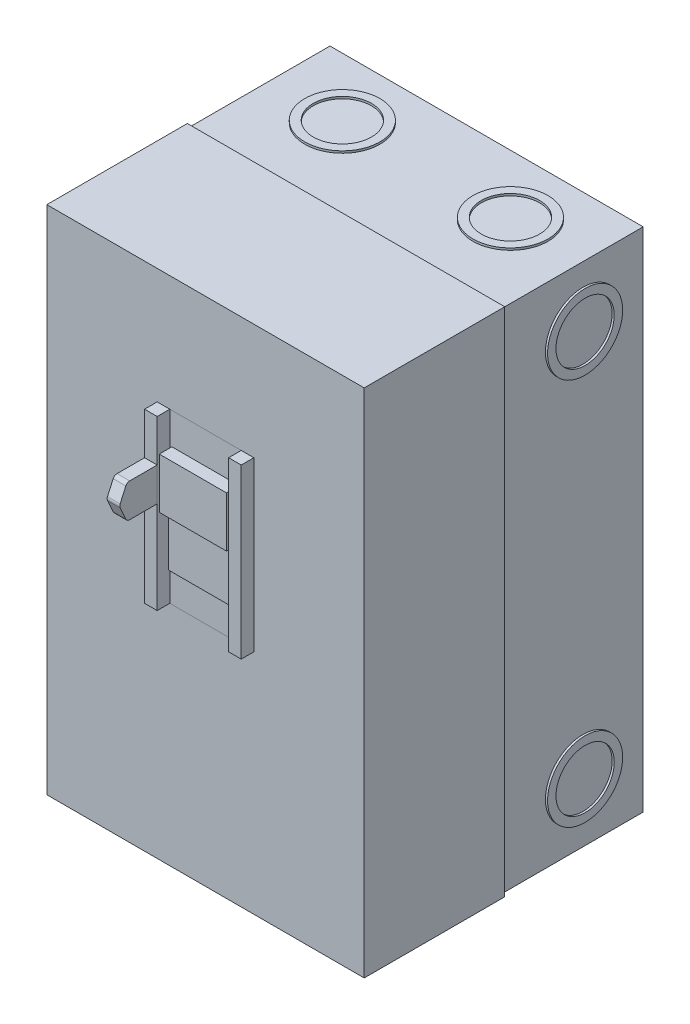
SolidWorks part; units mm, degrees
ref_plane "Front Plane" through (0, 0, 0) normal (0, 0, 1) x (1, 0, 0)
ref_plane "Top Plane" through (0, 0, 0) normal (0, 1, 0) x (1, 0, 0)
ref_plane "Right Plane" through (0, 0, 0) normal (1, 0, 0) x (0, 0, -1)
sketch "Sketch2" plane through (0, 0, 0) normal (1, 0, 0) x (0, 0, -1)
  line L0 (0, 0) -> (0, -95123.7541) construction
  line L1 (0, 0) -> (-95123.7541, 0) construction
  line L2 (0, -95.7262) -> (0, 95.7262)
  line L3 (0, 95.7262) -> (-53.086, 95.7262)
  line L4 (-53.086, 95.7262) -> (-53.086, 96.52)
  line L5 (-53.086, 96.52) -> (-106.172, 96.52)
  line L6 (-106.172, 96.52) -> (-106.172, -96.52)
  line L7 (-106.172, 0) -> (-110.9345, 0)
  line L8 (-53.086, -95.7262) -> (-53.086, -96.52)
  line L9 (0, -95.7262) -> (-53.086, -95.7262)
  line L10 (-53.086, -96.52) -> (-106.172, -96.52)
  line L11 (-53.086, 95.7262) -> (-53.086, -95.7262) construction
  line L12 (0, 0) -> (3.175, 0)
  line L13 (-22.733, 95.7262) -> (-22.733, -95.7262) construction
  circle A0 centre (-22.733, 73.152) radius 11.0109
  circle A1 centre (-22.733, 73.152) radius 14.1859
  circle A2 centre (-22.733, -73.152) radius 14.1859
  circle A3 centre (-22.733, -73.152) radius 11.0109
  point P13 (0, 0)
  dimension "D1" = 3.175
sketch "Sketch3" plane through (0, 0, 0) normal (0, 0, 1) x (1, 0, 0)
  line L0 (0, 0) -> (-49231.0849, 0) construction
  line L1 (0, 0) -> (0, -49231.0849) construction
  line L3 (31.75, 95.7262) -> (31.75, -95.7262) construction
  line L4 (-18.2563, 52.832) -> (18.2562, 52.832)
  line L5 (-18.2563, 52.832) -> (-18.2562, -10.668)
  line L6 (-18.2562, -10.668) -> (18.2563, -10.668)
  line L7 (18.2562, 52.832) -> (18.2563, -10.668)
  line L8 (-18.2563, 52.832) -> (18.2563, -10.668) construction
  line L9 (-18.2562, -10.668) -> (18.2562, 52.832) construction
  line L10 (-59.944, 95.7262) -> (59.944, 95.7262)
  line L11 (-59.944, 95.7262) -> (-59.944, -95.7262)
  line L12 (-59.944, -95.7262) -> (59.944, -95.7262)
  line L13 (59.944, 95.7262) -> (59.944, -95.7262)
  line L14 (-59.944, 95.7262) -> (59.944, -95.7262) construction
  line L15 (-59.944, -95.7262) -> (59.944, 95.7262) construction
  circle A0 centre (41.275, 76.2) radius 2.794
  circle A1 centre (-41.275, 76.2) radius 2.794
  circle A2 centre (41.275, -76.2) radius 2.794
  circle A3 centre (-41.275, -76.2) radius 2.794
  point P5 (-41.275, 76.2)
  point P6 (41.275, 76.2)
  point P7 (41.275, -76.2)
  point P8 (-41.275, -76.2)
  point P9 (0, 21.082)
  point P14 (0, 0)
  dimension "MOUNTING HOLE DIA" = 5.588
  dimension "MOUNTING HOLE VERTICAL DISTANCE" = 152.4
  dimension "MOUNTING HOLE HORIZONTAL DISTANCE" = 82.55
  dimension "BUTTON CAVITY DISTANCE FROM CENTER" = 21.082
  dimension "BUTTON CAVITY HEIGHT" = 63.5
  dimension "BUTTON CAVITY WIDTH" = 36.5125
  dimension "BOX WIDTH" = 119.888
  dimension "HORIZONTAL KNOCKOUT DISTANCE FROM CENTER" = 31.75
sketch "Sketch4" plane through (0, 0, 0) normal (0, 0, 1) x (1, 0, 0)
  line L0 (59.944, 95.7262) -> (59.944, -95.7262) construction
  line L1 (-59.1502, -95.7262) -> (59.1502, -95.7262)
  line L2 (-59.1502, -95.7262) -> (-59.1502, 95.7262)
  line L3 (-59.1502, 95.7262) -> (59.1502, 95.7262)
  line L4 (59.1502, -95.7262) -> (59.1502, 95.7262)
  line L5 (-59.1502, -95.7262) -> (59.1502, 95.7262) construction
  line L6 (-59.1502, 95.7262) -> (59.1502, -95.7262) construction
  point P0 (0, 0)
  dimension "D1" = 0.7937
extrude "Boss-Extrude1" add sketch "Sketch4" along normal up to vertex (53.086 mm away) up to point (0, 95.7262, 53.086)
sketch "Sketch5" plane through (0, 0, 53.086) normal (0, 0, 1) x (1, 0, 0)
  line L0 (59.944, 95.7262) -> (59.944, -95.7262) construction
  line L1 (-59.944, -96.52) -> (59.944, -96.52)
  line L2 (-59.944, -96.52) -> (-59.944, 96.52)
  line L3 (-59.944, 96.52) -> (59.944, 96.52)
  line L4 (59.944, -96.52) -> (59.944, 96.52)
  line L5 (-59.944, -96.52) -> (59.944, 96.52) construction
  line L6 (-59.944, 96.52) -> (59.944, -96.52) construction
  point P0 (0, 0)
extrude "Boss-Extrude2" add sketch "Sketch5" along normal up to vertex (53.086 mm away) up to point (0, 96.52, 106.172)
sketch "Sketch6" plane through (0, 0, 0) normal (0, 0, -1) x (-1, 0, 0)
  circle A0 centre (41.275, 73.025) radius 12.7
  circle A1 centre (-41.275, 73.025) radius 12.7
  circle A2 centre (41.275, -76.2) radius 9.525
  circle A3 centre (-41.275, -76.2) radius 9.525
  dimension "D1" = 25.4
  dimension "D2" = 19.05
  dimension "D3" = 3.175
extrude "Boss-Extrude3" add sketch "Sketch6" along normal blind 3.175
fillet "Fillet1" radius 3.175 4 edges at (31.75, -76.2, -3.175) (-50.8, -76.2, -3.175) (-53.975, 73.025, -3.175) (28.575, 73.025, -3.175)
sketch "Sketch7" plane through (0, 0, -3.175) normal (0, 0, -1) x (-1, 0, 0)
  circle A0 centre (-41.275, 76.2) radius 2.794 construction
  circle A1 centre (41.275, 76.2) radius 2.794 construction
  circle A2 centre (41.275, -76.2) radius 2.794 construction
  circle A3 centre (-41.275, -76.2) radius 2.794 construction
  circle A4 centre (-41.275, 76.2) radius 2.794
  circle A5 centre (41.275, 76.2) radius 2.794
  circle A6 centre (41.275, -76.2) radius 2.794
  circle A7 centre (-41.275, -76.2) radius 2.794
extrude "Cut-Extrude1" cut sketch "Sketch7" against normal blind 6.35
sketch "Sketch8" plane through (0, 0, -3.175) normal (0, 0, -1) x (-1, 0, 0)
  line L0 (-41.275, 76.2) -> (-41.275, 69.0563) construction
  line L1 (-46.3991, 71.2047) -> (-43.8517, 77.2803)
  line L2 (-38.6983, 77.2803) -> (-36.1509, 71.2047)
  line L3 (0, 95.7263) -> (0, -95.7262) construction
  line L4 (59.944, 95.7262) -> (-59.944, 95.7262) construction
  line L5 (59.944, -95.7262) -> (-59.944, -95.7262) construction
  line L6 (41.275, 76.2) -> (41.275, 69.0563) construction
  line L7 (38.6983, 77.2803) -> (36.1509, 71.2047)
  line L8 (46.3991, 71.2047) -> (43.8517, 77.2803)
  arc A0 (-46.3991, 71.2047) -> (-36.1509, 71.2047) centre (-41.275, 69.0563) ccw
  arc A1 (43.8517, 77.2803) -> (38.6983, 77.2803) centre (41.275, 76.2) ccw
  circle A2 centre (-41.275, 76.2) radius 2.794 construction
  arc A3 (-43.8517, 77.2803) -> (-38.6983, 77.2803) centre (-41.275, 76.2) cw
  arc A4 (46.3991, 71.2047) -> (36.1509, 71.2047) centre (41.275, 69.0563) cw
  dimension "D1" = 5.5562
  dimension "D2" = 7.1437
extrude "Cut-Extrude2" cut sketch "Sketch8" against normal up to surface (6.35 mm away) up to face at (-44.069, 76.2, 3.175)
sketch "Sketch9" plane through (59.1502, 0, 0) normal (1, 0, 0) x (0, 0, -1)
  line L4 (0, -95.7262) -> (0, 95.7262)
  line L5 (0, 95.7262) -> (-53.086, 95.7262)
  line L6 (-53.086, 95.7262) -> (-53.086, -95.7262)
  line L7 (-53.086, -95.7262) -> (0, -95.7262)
  line L8 (0, -95.7262) -> (0, 95.7262)
  line L9 (0, 95.7262) -> (-53.086, 95.7262)
  line L10 (-53.086, 95.7262) -> (-53.086, -95.7262)
  line L11 (-53.086, -95.7262) -> (0, -95.7262)
  circle A0 centre (-22.733, 73.152) radius 14.1859 construction
  circle A1 centre (-22.733, 73.152) radius 14.1859
  circle A2 centre (-22.733, 73.152) radius 11.0109 construction
  circle A3 centre (-22.733, -73.152) radius 11.0109 construction
  circle A4 centre (-22.733, -73.152) radius 14.1859 construction
  circle A5 centre (-22.733, 73.152) radius 11.0109
  circle A6 centre (-22.733, -73.152) radius 11.0109
  circle A7 centre (-22.733, -73.152) radius 14.1859
  dimension "D1" = 0
extrude "Boss-Extrude4" add sketch "Sketch9" along normal up to vertex (0.7937 mm away) contours A1 A5 | A7 A6 region at (59.1502, 73.152, 36.5177) region at (59.1502, -73.152, 36.5177) up to point (59.944, 95.7262, 0)
mirror "Mirror1" about plane through (0, 0, 0) normal (1, 0, 0) of "Boss-Extrude4"
sketch "Sketch10" plane through (0, 95.7262, 0) normal (0, 1, 0) x (1, 0, 0)
  line L0 (-59.1502, -22.733) -> (59.1502, -22.733) construction
  line L1 (-59.1502, -53.086) -> (-59.1502, 0) construction
  line L2 (59.1502, -53.086) -> (59.1502, 0) construction
  line L3 (0, 0) -> (0, -50.546) construction
  line L4 (-59.944, 0) -> (59.944, 0) construction
  line L5 (0, 0) -> (0, -53.086) construction
  circle A0 centre (31.75, -22.733) radius 11.0109
  circle A1 centre (31.75, -22.733) radius 14.1859
  circle A2 centre (-31.75, -22.733) radius 14.1859
  circle A3 centre (-31.75, -22.733) radius 11.0109
  dimension "D1" = 3.175
  dimension "D2" = 22.0218
extrude "Boss-Extrude5" add sketch "Sketch10" along normal up to vertex (0.7937 mm away) up to point (0, 96.52, 53.086)
mirror "Mirror2" about plane through (0, 0, 0) normal (0, 1, 0) of "Boss-Extrude5"
sketch "Sketch11" plane through (0, 0, 106.172) normal (0, 0, 1) x (1, 0, 0)
  line L0 (-18.2563, 52.832) -> (-18.2562, -10.668) construction
  line L1 (-18.2562, -10.668) -> (18.2563, -10.668) construction
  line L2 (18.2562, 52.832) -> (18.2563, -10.668) construction
  line L3 (-18.2563, 52.832) -> (18.2562, 52.832) construction
  line L4 (59.944, -96.52) -> (59.944, 96.52)
  line L5 (59.944, 96.52) -> (-59.944, 96.52)
  line L6 (-59.944, 96.52) -> (-59.944, -96.52)
  line L7 (-59.944, -96.52) -> (59.944, -96.52)
  line L8 (59.944, -96.52) -> (59.944, 96.52)
  line L9 (59.944, 96.52) -> (-59.944, 96.52)
  line L10 (-59.944, 96.52) -> (-59.944, -96.52)
  line L11 (-59.944, -96.52) -> (59.944, -96.52)
  line L12 (-18.2563, 52.832) -> (-18.2562, -10.668)
  line L13 (-18.2562, -10.668) -> (18.2563, -10.668)
  line L14 (18.2562, 52.832) -> (18.2563, -10.668)
  line L15 (-18.2563, 52.832) -> (18.2562, 52.832)
  dimension "D1" = 0
extrude "Cut-Extrude3" cut sketch "Sketch11" against normal blind 1.27 contours L15 L12 L13 L14 region at (0, 21.082, 106.172)
sketch "Sketch12" plane through (0, 52.832, 0) normal (0, -1, 0) x (1, 0, 0)
  line L0 (-18.2562, 104.902) -> (-18.2562, 110.9345)
  line L1 (-18.2562, 110.9345) -> (-13.4937, 110.9345)
  line L2 (-13.4937, 110.9345) -> (-13.4937, 106.172)
  line L3 (-59.944, 106.172) -> (59.944, 106.172) construction
  line L4 (-13.4937, 106.172) -> (0, 106.172)
  line L5 (0, 104.902) -> (0, 53.086) construction
  line L6 (-18.2562, 104.902) -> (18.2563, 104.902) construction
  line L7 (-59.944, 53.086) -> (59.944, 53.086) construction
  line L8 (-18.2562, 104.902) -> (0, 104.902)
  line L9 (13.4937, 106.172) -> (0, 106.172)
  line L10 (13.4937, 110.9345) -> (13.4937, 106.172)
  line L11 (18.2562, 110.9345) -> (13.4937, 110.9345)
  line L12 (18.2563, 104.902) -> (18.2562, 110.9345)
  line L13 (18.2563, 104.902) -> (0, 104.902)
  dimension "D1" = 26.9875
extrude "Boss-Extrude6" add sketch "Sketch12" along normal up to surface (63.5 mm away) separate body up to face at (0, -10.668, 105.537)
sketch "Sketch13" plane through (0, 0, 106.172) normal (0, 0, 1) x (1, 0, 0)
  line L0 (-13.4938, 21.082) -> (13.4938, 21.082) construction
  line L1 (-13.4937, -10.668) -> (-13.4937, 52.832) construction
  line L2 (13.4937, -10.668) -> (13.4937, 52.832) construction
  line L3 (0, 52.832) -> (0, -10.668) construction
  line L4 (-18.2563, 52.832) -> (18.2562, 52.832) construction
  line L5 (-18.2562, -10.668) -> (18.2563, -10.668) construction
  line L6 (12.7, 40.9258) -> (-12.7, 40.9258)
  line L7 (12.7, 20.2882) -> (-12.7, 20.2882)
  line L8 (12.7, 20.2882) -> (12.7, 1.2382)
  line L9 (12.7, 1.2382) -> (-12.7, 1.2382)
  line L10 (-12.7, 20.2882) -> (-12.7, 1.2382)
  line L11 (12.7, 20.2882) -> (-12.7, 1.2382) construction
  line L12 (12.7, 1.2382) -> (-12.7, 20.2882) construction
  line L13 (-12.7, 21.8758) -> (-12.7, 40.9258)
  line L14 (12.7, 21.8758) -> (-12.7, 21.8758)
  line L15 (12.7, 21.8758) -> (12.7, 40.9258)
  line L16 (12.7, 40.9258) -> (-12.7, 21.8758) construction
  line L17 (12.7, 21.8758) -> (-12.7, 40.9258) construction
  point P12 (0, 10.7632)
  point P21 (0, 31.4008)
  dimension "D1" = 25.4
  dimension "D2" = 19.05
  dimension "D3" = 11.9062
extrude "Cut-Extrude4" cut sketch "Sketch13" against normal up to next (1.27 mm away)
sketch "Sketch14" plane through (0, 0, 104.902) normal (0, 0, 1) x (1, 0, 0)
  line L0 (-12.7, 21.8758) -> (12.7, 21.8758) construction
  line L1 (12.7, 21.8758) -> (12.7, 40.9258) construction
  line L2 (12.7, 40.9258) -> (-12.7, 40.9258) construction
  line L3 (-12.7, 40.9258) -> (-12.7, 21.8758) construction
  line L4 (-12.7, 21.8758) -> (12.7, 21.8758)
  line L5 (12.7, 21.8758) -> (12.7, 40.9258)
  line L6 (12.7, 40.9258) -> (-12.7, 40.9258)
  line L7 (-12.7, 40.9258) -> (-12.7, 21.8758)
extrude "Boss-Extrude7" add sketch "Sketch14" along normal up to surface (6.0325 mm away) separate body up to face at (15.875, 21.082, 110.9345)
sketch "Sketch15" plane through (0, 0, 104.902) normal (0, 0, 1) x (1, 0, 0)
  line L4 (12.7, 20.2882) -> (12.7, 1.2382)
  line L5 (-12.7, 20.2882) -> (12.7, 20.2882)
  line L6 (-12.7, 20.2882) -> (-12.7, 1.2382)
  line L7 (12.7, 1.2382) -> (-12.7, 1.2382)
  line L8 (12.7, 20.2882) -> (-12.7, 20.2882) construction
  line L9 (12.7, 1.2382) -> (12.7, 20.2882) construction
  line L10 (-12.7, 1.2382) -> (12.7, 1.2382) construction
extrude "Boss-Extrude8" add sketch "Sketch15" along normal offset from surface (2.54 mm away) 1.27 separate body up to face at (0, 31.4008, 106.172) offset beyond the face yes
sketch "Sketch16" plane through (-18.2562, 0, 0) normal (-1, 0, 0) x (0, 0, 1)
  line L0 (110.9345, 30.607) -> (125.222, 30.607) construction
  line L1 (110.9345, -10.668) -> (110.9345, 52.832) construction
  line L2 (124.9288, 31.2585) -> (122.7857, 36.021)
  line L3 (121.338, 36.957) -> (110.9345, 36.957)
  line L4 (124.9288, 29.9555) -> (122.7857, 25.193)
  line L5 (121.338, 24.257) -> (110.9345, 24.257)
  line L6 (110.9345, 36.957) -> (110.9345, 24.257)
  line L7 (110.9345, 52.832) -> (104.902, 52.832) construction
  arc A0 (122.7857, 25.193) -> (121.338, 24.257) centre (121.338, 25.8445) cw
  arc A1 (124.9288, 31.2585) -> (124.9288, 29.9555) centre (123.4812, 30.607) cw
  arc A2 (122.7857, 36.021) -> (121.338, 36.957) centre (121.338, 35.3695) ccw
  point P12 (122.3645, 24.257)
  point P18 (122.3645, 36.957)
  dimension "D4" = 1.5875
  dimension "D1" = 15.875
  dimension "D2" = 12.7
  dimension "D3" = 14.2875
  dimension "D5" = 11.43
extrude "Boss-Extrude9" add sketch "Sketch16" against normal up to surface (4.7625 mm away) separate body up to face at (-13.4937, 21.082, 108.5532)
sketch "Sketch17" plane through (0, 0, 0) normal (1, 0, 0) x (0, 0, -1)
  line L0 (-36.576, -95.7262) -> (-52.451, -95.7262)
  line L1 (0, -95.7262) -> (-53.086, -95.7262) construction
  line L2 (-52.451, -95.7262) -> (-52.451, -111.6013)
  line L3 (-52.451, -111.6013) -> (-50.8635, -111.6013)
  line L4 (-50.8635, -111.6013) -> (-50.8635, -97.3137)
  line L5 (-50.8635, -97.3137) -> (-36.576, -97.3137)
  line L6 (-36.576, -97.3137) -> (-36.576, -95.7262)
  line L7 (-69.596, -96.52) -> (-69.596, -112.395)
  line L8 (-53.086, -96.52) -> (-106.172, -96.52) construction
  line L9 (-69.596, -112.395) -> (-68.0085, -112.395)
  line L10 (-68.0085, -112.395) -> (-68.0085, -98.1075)
  line L11 (-68.0085, -98.1075) -> (-55.3085, -98.1075)
  line L12 (-55.3085, -98.1075) -> (-55.3085, -112.395)
  line L13 (-55.3085, -112.395) -> (-53.721, -112.395)
  line L14 (-53.721, -112.395) -> (-53.721, -96.52)
  line L15 (-53.721, -96.52) -> (-69.596, -96.52)
  line L16 (-61.6585, -98.1075) -> (-61.6585, -96.52) construction
  line L17 (-53.086, -95.7262) -> (-53.086, -96.52) construction
  dimension "D1" = 15.875
  dimension "D2" = 0.635
  dimension "D3" = 0.635
  dimension "D4" = 1.5875
extrude "Boss-Extrude10" add sketch "Sketch17" along normal mid plane 38.1 separate body
fillet "Fillet2" radius 3.175 4 edges at (-19.05, -111.6013, 51.6572) (-19.05, -96.52, 36.576) (19.05, -96.52, 36.576) (19.05, -111.6013, 51.6572)
sketch "Sketch18" plane through (0, 0, 55.3085) normal (0, 0, 1) x (1, 0, 0)
  line L0 (-19.05, -98.1075) -> (-19.05, -112.395) construction
  line L1 (19.05, -112.395) -> (-3.175, -112.395)
  line L2 (19.05, -112.395) -> (19.05, -101.2825)
  line L3 (19.05, -101.2825) -> (-3.175, -101.2825)
  line L4 (-3.175, -112.395) -> (-3.175, -101.2825)
  dimension "D1" = 15.875
  dimension "D2" = 11.1125
extrude "Cut-Extrude5" cut sketch "Sketch18" against normal blind 38.1
sketch "Sketch19" plane through (0, 0, 69.596) normal (0, 0, 1) x (1, 0, 0)
  line L0 (19.05, -96.52) -> (-19.05, -96.52) construction
  line L1 (-19.05, -112.395) -> (3.175, -112.395)
  line L2 (-19.05, -112.395) -> (-19.05, -96.52)
  line L3 (-19.05, -96.52) -> (3.175, -96.52)
  line L4 (3.175, -112.395) -> (3.175, -96.52)
  line L5 (19.05, -96.52) -> (19.05, -112.395) construction
  dimension "D1" = 15.875
extrude "Cut-Extrude6" cut sketch "Sketch19" against normal blind 3.175
fillet "Fillet3" radius 3.175 6 edges at (-3.175, -101.2825, 54.5147) (-19.05, -97.3137, 66.421) (19.05, -112.395, 68.8022) (3.175, -112.395, 68.8023) (-3.175, -112.395, 54.5147) (-19.05, -112.395, 54.5147)
sketch "Sketch20" plane through (0, 0, 55.3085) normal (0, 0, 1) x (1, 0, 0)
  line L0 (-11.1125, -112.395) -> (-11.1125, -98.1075) construction
  line L1 (-6.35, -112.395) -> (-15.875, -112.395) construction
  line L2 (19.05, -98.1075) -> (-19.05, -98.1075) construction
  circle A0 centre (-11.1125, -105.2512) radius 5.08
  dimension "D1" = 10.16
extrude "Cut-Extrude7" cut sketch "Sketch20" against normal through all
sketch "Sketch21" plane through (0, 0, 69.596) normal (0, 0, 1) x (1, 0, 0)
  line L0 (11.1125, -112.395) -> (11.1125, -96.52) construction
  line L1 (15.875, -112.395) -> (6.35, -112.395) construction
  line L2 (19.05, -96.52) -> (3.175, -96.52) construction
  circle A0 centre (11.1125, -104.4575) radius 2.159
  dimension "D1" = 4.318
extrude "Cut-Extrude8" cut sketch "Sketch21" against normal through all
sketch "Sketch22" plane through (0, 0, 69.596) normal (0, 0, 1) x (1, 0, 0)
  line L1 (6.5298, -104.4575) -> (8.8211, -108.4262)
  line L2 (8.8211, -108.4262) -> (13.4039, -108.4262)
  line L3 (13.4039, -108.4262) -> (15.6952, -104.4575)
  line L4 (15.6952, -104.4575) -> (13.4039, -100.4887)
  line L5 (13.4039, -100.4887) -> (8.8211, -100.4887)
  line L6 (8.8211, -100.4887) -> (6.5298, -104.4575)
  circle A0 centre (11.1125, -104.4575) radius 3.9687 construction
  dimension "D1" = 7.9375
extrude "Boss-Extrude11" add sketch "Sketch22" along normal blind 3.175 separate body
sketch "Sketch23" plane through (0, -108.4263, 0) normal (0, -1, 0) x (1, 0, 0)
  line L0 (11.1125, 72.771) -> (11.1125, 69.596) construction
  line L1 (8.8211, 72.771) -> (13.4039, 72.771) construction
  line L2 (15.875, 69.596) -> (6.35, 69.596) construction
  line L4 (11.43, 71.501) -> (10.795, 71.501)
  line L5 (11.43, 71.501) -> (11.43, 72.771)
  line L6 (11.43, 72.771) -> (10.795, 72.771)
  line L7 (10.795, 71.501) -> (10.795, 72.771)
  line L8 (11.43, 71.501) -> (10.795, 72.771) construction
  line L9 (11.43, 72.771) -> (10.795, 71.501) construction
  point P6 (11.1125, 72.136)
  dimension "D1" = 0.635
  dimension "D2" = 1.27
extrude "Cut-Extrude9" cut sketch "Sketch23" against normal up to next (7.9375 mm away)
sketch "Sketch24" plane through (0, 0, 69.596) normal (0, 0, -1) x (-1, 0, 0)
  line L6 (-6.5298, -104.4575) -> (-8.8211, -100.4888)
  line L7 (-8.8211, -100.4888) -> (-13.4039, -100.4888)
  line L8 (-13.4039, -100.4888) -> (-15.6952, -104.4575)
  line L9 (-15.6952, -104.4575) -> (-13.4039, -108.4263)
  line L10 (-13.4039, -108.4263) -> (-8.8211, -108.4263)
  line L11 (-8.8211, -108.4263) -> (-6.5298, -104.4575)
  line L12 (-6.5298, -104.4575) -> (-8.8211, -100.4888)
  line L13 (-8.8211, -100.4888) -> (-13.4039, -100.4888)
  line L14 (-13.4039, -100.4888) -> (-15.6952, -104.4575)
  line L15 (-15.6952, -104.4575) -> (-13.4039, -108.4263)
  line L16 (-13.4039, -108.4263) -> (-8.8211, -108.4263)
  line L17 (-8.8211, -108.4263) -> (-6.5298, -104.4575)
  circle A0 centre (-11.1125, -104.4575) radius 2.159 construction
  circle A1 centre (-11.1125, -104.4575) radius 2.159
  circle A2 centre (-11.1125, -104.4575) radius 2.032
  dimension "D1" = 0
  dimension "D2" = 0.127
extrude "Boss-Extrude12" add sketch "Sketch24" along normal blind 19.05 contours A2 region at (11.1125, -104.4575, 69.596)
equation "\"D1@Sketch4\"=\"TOP BOTTOM WIDTH DIFFERANCE@Sketch2\""
equation "\"D1@Sketch10\"=\"D1@Sketch2\""
equation "\"D2@Sketch10\"=\"KNOCKOUT DIA@Sketch2\""
equation "\"D3@Sketch17\"=\"D2@Sketch17\""
